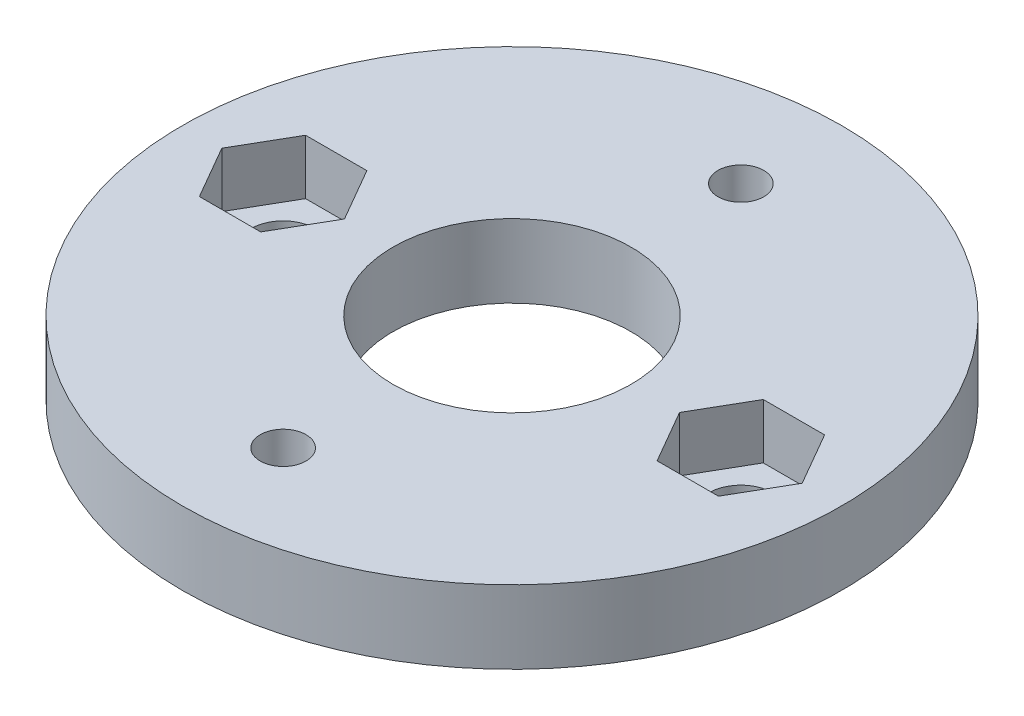
SolidWorks part; units mm, degrees
ref_plane "Спереди" through (0, 0, 0) normal (0, 0, 1) x (1, 0, 0)
ref_plane "Сверху" through (0, 0, 0) normal (0, 1, 0) x (1, 0, 0)
ref_plane "Справа" through (0, 0, 0) normal (1, 0, 0) x (0, 0, -1)
sketch "Эскиз1" plane through (0, 0, 0) normal (0, 1, 0) x (1, 0, 0)
  circle A0 centre (0, 0) radius 18
  circle A1 centre (0, 0) radius 6.5
  dimension "D1" = 13
  dimension "D2" = 36
extrude "тело" add sketch "Эскиз1" along normal blind 4
sketch "Эскиз2" plane through (0, 4, 0) normal (0, 1, 0) x (1, 0, 0)
  line L1 (15.8486, 0) -> (14.1743, 2.9)
  line L2 (14.1743, 2.9) -> (10.8257, 2.9)
  line L3 (10.8257, 2.9) -> (9.1514, 0)
  line L4 (9.1514, 0) -> (10.8257, -2.9)
  line L5 (10.8257, -2.9) -> (14.1743, -2.9)
  line L6 (14.1743, -2.9) -> (15.8486, 0)
  circle A0 centre (0, 0) radius 12.5 construction
  circle A1 centre (12.5, 0) radius 2.9 construction
  dimension "D1" = 25
  dimension "D2" = 5.8
extrude "паз для гаек" cut sketch "Эскиз2" against normal blind 3
sketch "Эскиз3" plane through (0, 1, 0) normal (0, 1, 0) x (1, 0, 0)
  line L0 (9.1514, 0) -> (15.8486, 0) construction
  circle A0 centre (12.5, 0) radius 1.75
  dimension "D1" = 3.5
extrude "сквозное отверстие под гайкой" cut sketch "Эскиз3" against normal through all
sketch "Эскиз4" plane through (0, 4, 0) normal (0, 1, 0) x (1, 0, 0)
  circle A0 centre (0, 0) radius 12.5 construction
  circle A1 centre (0, 12.5) radius 1.25
  dimension "D1" = 25
  dimension "D2" = 2.5
extrude "отверстие для шурупа" cut sketch "Эскиз4" against normal through all
pattern_circular "Круговой массив1" count 2 every 180 about axis through (0, 4, 0) along (0, -1, 0) of "паз для гаек", "сквозное отверстие под гайкой", "отверстие для шурупа"
